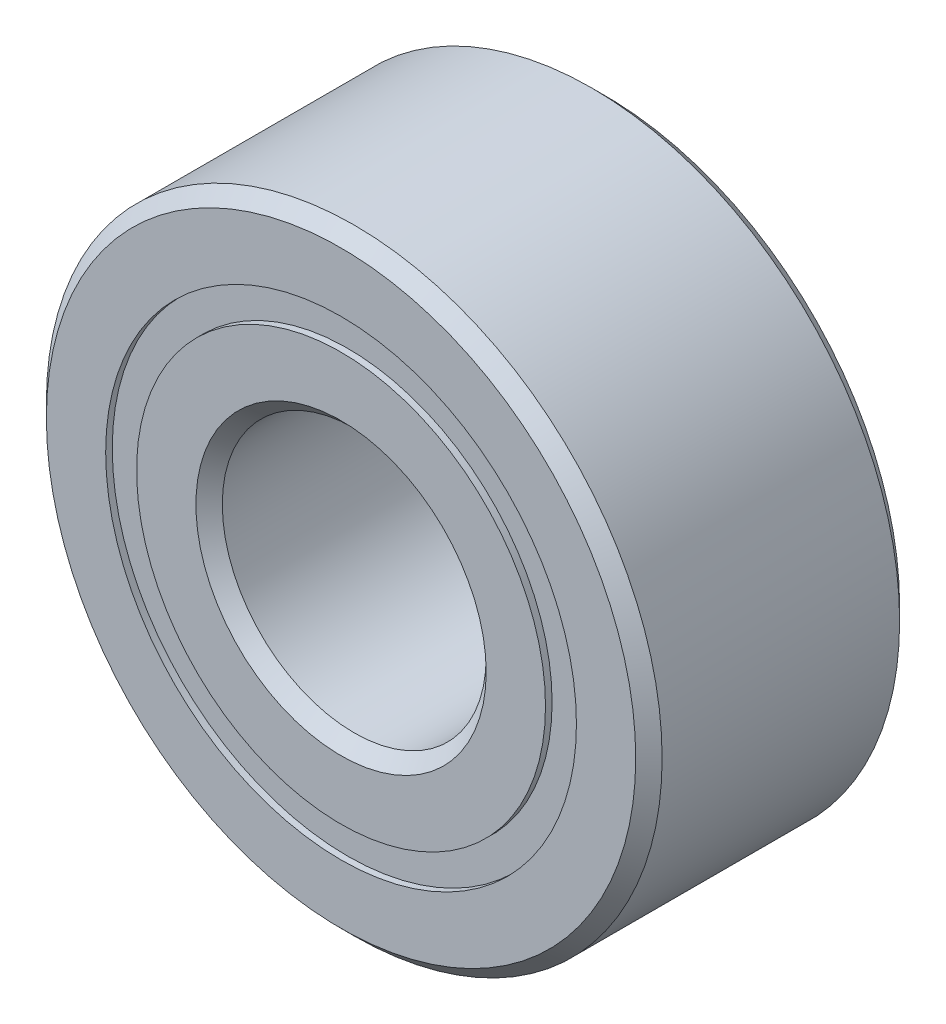
SolidWorks part; units mm, degrees
material "Alloy Steel"
ref_plane "Front Plane" through (0, 0, 0) normal (0, 0, 1) x (1, 0, 0)
ref_plane "Top Plane" through (0, 0, 0) normal (0, 1, 0) x (1, 0, 0)
ref_plane "Right Plane" through (0, 0, 0) normal (1, 0, 0) x (0, 0, -1)
sketch "Sketch1" plane through (0, 0, 0) normal (1, 0, 0) x (0, 0, -1)
  line L0 (-1.5, 0) -> (1.5, 0) construction
  line L1 (0, 3.5) -> (0, -3.5) construction
  line L2 (1.35, 3.5) -> (-1.35, 3.5)
  line L3 (-1.35, 3.5) -> (-1.5, 3.35)
  line L4 (-1.5, 3.35) -> (-1.5, 2.6758)
  line L5 (-1.5, 2.6758) -> (-0.6667, 2.6758)
  line L6 (1.5, 2.6758) -> (0.6667, 2.6758)
  line L7 (1.5, 3.35) -> (1.5, 2.6758)
  line L8 (1.35, 3.5) -> (1.5, 3.35)
  line L9 (0, 3.5) -> (0, 2.5) construction
  line L10 (0, 2.5) -> (0, 1.5) construction
  arc A0 (-0.6667, 2.6758) -> (0.6667, 2.6758) centre (0, 2.5) cw
  point P14 (0, 1.5)
  dimension "D3" = 1.3333
  dimension "D1" = 45
  dimension "Width" = 3
  dimension "OD" = 7
  dimension "D2" = 0.15
  dimension "Shaft Dia" = 3
  dimension "D4" = 0.1758
revolve "Revolve1" add sketch "Sketch1" angle 360 about L0
sketch "Sketch3" plane through (0, 0, 0) normal (1, 0, 0) x (0, 0, -1)
  line L0 (-1.5, 2.3242) -> (-0.6667, 2.3242)
  line L1 (0, 3.5) -> (0, -3.5) construction
  line L2 (-1.5, 3.35) -> (-1.5, 2.6758) construction
  line L3 (-1.5, 2.3242) -> (-1.5, 1.65)
  line L4 (-1.35, 3.5) -> (-1.5, 3.35) construction
  line L5 (-1.5, 1.65) -> (-1.35, 1.5)
  line L6 (-1.35, 1.5) -> (1.35, 1.5)
  line L7 (1.35, 3.5) -> (1.35, -3.5) construction
  line L8 (1.35, 1.5) -> (1.5, 1.65)
  line L9 (1.5, -3.35) -> (1.5, 3.35) construction
  line L10 (1.5, 1.65) -> (1.5, 2.3242)
  line L11 (1.5, 2.3242) -> (0.6667, 2.3242)
  line L13 (1.35, 3.5) -> (1.5, 3.35) construction
  arc A0 (0.6667, 2.6758) -> (-0.6667, 2.6758) centre (0, 2.5) ccw construction
  arc A1 (0.6667, 2.3242) -> (-0.6667, 2.3242) centre (0, 2.5) cw
revolve "Revolve3" add sketch "Sketch3" angle 360 about L0
sketch "Sketch4" plane through (0, 0, 0) normal (1, 0, 0) x (0, 0, -1)
  line L0 (-0.6895, 2.5) -> (0.6895, 2.5)
  arc A2 (-0.6895, 2.5) -> (0.6895, 2.5) centre (0, 2.5) cw
  arc A3 (0.6667, 2.6758) -> (-0.6667, 2.6758) centre (0, 2.5) ccw construction
revolve "Revolve4" add sketch "Sketch4" angle 360 about L0
ref_axis "Axis1" through (0, 0, -1.5) along (0, 0, 1)
pattern_circular "CirPattern1" count 12 every 30 about axis through (0, 0, -1.5) along (0, 0, 1) of bodies 104
sketch "Sketch5" plane through (0, 0, 0) normal (1, 0, 0) x (0, 0, -1)
  line L0 (-1.5, 2.6758) -> (-0.6667, 2.6758) construction
  line L1 (-1.425, 2.6758) -> (-0.6895, 2.6758)
  line L2 (-1.425, 2.6758) -> (-1.425, 2.3242)
  line L3 (-1.425, 2.3242) -> (-0.6895, 2.3242)
  line L4 (-0.6895, 2.6758) -> (-0.6895, 2.3242)
  line L5 (-1.5, 2.3242) -> (-0.6667, 2.3242) construction
  line L6 (1.5, 2.6758) -> (0.6667, 2.6758) construction
  line L7 (1.425, 2.6758) -> (0.6895, 2.6758)
  line L8 (1.425, 2.6758) -> (1.425, 2.3242)
  line L9 (1.425, 2.3242) -> (0.6895, 2.3242)
  line L10 (0.6895, 2.6758) -> (0.6895, 2.3242)
  line L11 (1.5, 2.3242) -> (0.6667, 2.3242) construction
  line L12 (-1.35, 3.5) -> (-1.5, 3.35) construction
  point P18 (-1.425, 3.425)
revolve "Revolve5" add sketch "Sketch5" angle 360 about L0
sketch "Sketch6" plane through (0, 0, 0) normal (1, 0, 0) x (0, 0, -1)
  line L0 (1.5, 0) -> (-1.5, 0) construction
  line L1 (1.5, 2.6758) -> (0.7126, 2.6758)
  line L2 (1.5, 2.6758) -> (1.5, 6.9469)
  line L3 (1.5, 6.9469) -> (0.7126, 6.9469)
  line L4 (0.7126, 2.6758) -> (0.7126, 6.9469)
  dimension "Th" = 0.7874
  dimension "Flange OD" = 13.8938
revolve "Revolve6" [suppressed] add sketch "Sketch6" angle 360 about L0
equation "\"D2@Sketch1\" = \"Width@Sketch1\"*.05"
equation "\"D3@Sketch1\" = \"Width@Sketch1\"/2.25"
equation "\"D4@Sketch1\" = (((\"OD@Sketch1\"-\"Width@Sketch1\")/2)/3.25)/3.5"
equation "\"D2@CirPattern1\" = 360/\"Balls@CirPattern1\""
